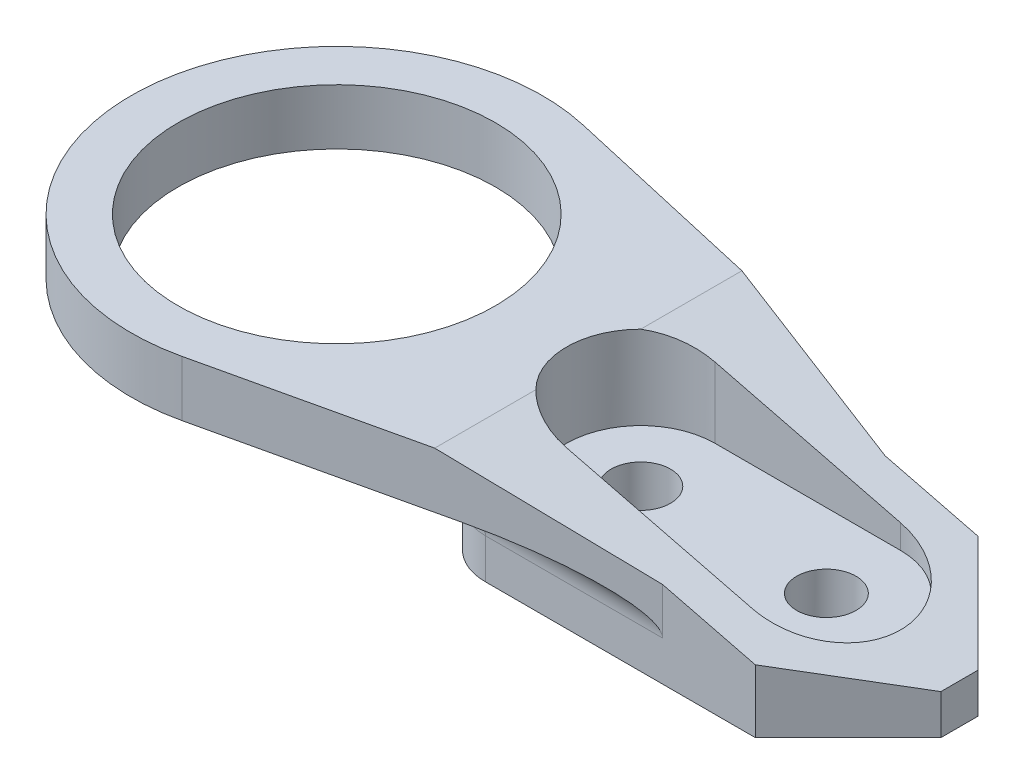
SolidWorks part; units mm, degrees
ref_plane "Front Plane" through (0, 0, 0) normal (0, 0, 1) x (1, 0, 0)
ref_plane "Top Plane" through (0, 0, 0) normal (0, 1, 0) x (1, 0, 0)
ref_plane "Right Plane" through (0, 0, 0) normal (1, 0, 0) x (0, 0, -1)
sketch "Sketch1" plane through (0, 0, 0) normal (0, 0, 1) x (1, 0, 0)
  line L0 (0, 0) -> (0, 7.15)
  line L1 (0, 7.15) -> (25, 7.15)
  line L2 (25, 7.15) -> (25, 0)
  line L3 (25, 0) -> (0, 0)
extrude "Boss-Extrude1" add sketch "Sketch1" along normal blind 12
sketch "Sketch2" plane through (0, 7.15, 0) normal (0, 1, 0) x (1, 0, 0)
  line L0 (0, -6) -> (-8.5537, -6) construction
  line L1 (0, -12) -> (0, 0) construction
  line L3 (25, 0) -> (0, 0) construction
  line L5 (25, -12) -> (0, -12) construction
  line L8 (15, -6) -> (15, 0)
  line L11 (15, 0) -> (-6.0937, 4.8033)
  line L12 (15, -6) -> (15, -12)
  line L13 (15, -12) -> (-6.0937, -16.8033)
  arc A6 (-6.0937, 4.8033) -> (-6.0937, -16.8033) centre (-8.5537, -6) ccw
  line M4 (25, 0) -> (0, 0)
  line M5 (0, 0) -> (0, -12)
  line M6 (0, -12) -> (25, -12)
extrude "Boss-Extrude2" add sketch "Sketch2" against normal blind 3 contours M6 M5 M4 region at (-7.3107, 7.15, 6)
sketch "Sketch3" plane through (0, 4.15, 0) normal (0, -1, 0) x (1, 0, 0)
  circle A1 centre (-8.2201, 6) radius 11
extrude "Cut-Extrude1" cut sketch "Sketch3" along normal blind 21
fillet "Fillet1" radius 3 2 edges at (0.9994, 2.075, 0) (0.9994, 2.075, 12)
sketch "Sketch4" plane through (0, 4.15, 0) normal (0, -1, 0) x (1, 0, 0)
  circle A1 centre (-8.5537, 6) radius 8.55
extrude "Cut-Extrude2" cut sketch "Sketch4" against normal blind 10
chamfer "Chamfer1" distance 5 distance2 20 1 edges at (25, 7.15, 6) first distance on face at (25, 3.575, 6)
sketch "Sketch5" plane through (0, 0, 0) normal (0, -1, 0) x (-1, 0, 0)
  line L0 (-2.4547, -9) -> (-2.4547, -3)
  line L1 (-2.4547, -3) -> (-3.7108, -3)
  line L2 (-3.7108, -3) -> (-3.7108, -9)
  line L3 (-3.7108, -9) -> (-2.4547, -9)
  arc A0 (-5.4547, -12) -> (-2.5244, -8.3571) centre (-5.4547, -9) ccw construction
  arc A1 (-2.5244, -3.6429) -> (-5.4547, 0) centre (-5.4547, -3) ccw construction
extrude "Boss-Extrude3" add sketch "Sketch5" against normal blind 5
fillet "Fillet2" radius 2 5 edges at (10.2273, 4.15, 0) (10.2273, 4.15, 12) (3.3334, 4.15, 11.1213) (2.4547, 4.15, 6) (3.3334, 4.15, 0.8787)
chamfer "Chamfer2" distance 5 angle 45 2 edges at (25, 1.075, 12) (25, 1.075, 0)
sketch "Sketch6" plane through (0, 7.15, 0) normal (0, 1, 0) x (1, 0, 0)
  line L0 (-0.0037, -6) -> (7.8299, -6) construction
  line L1 (7.8299, -6) -> (17.8299, -6) construction
  circle A0 centre (-8.5537, -6) radius 8.55 construction
  circle A1 centre (7.8299, -6) radius 1.6
  circle A2 centre (17.8299, -6) radius 1.6
  dimension "D1" = 10
extrude "Cut-Extrude3" cut sketch "Sketch6" against normal blind 10
sketch "Sketch7" plane through (0, 7.15, 0) normal (0, 1, 0) x (1, 0, 0)
  line L0 (7.8299, -2) -> (17.8299, -2)
  line L1 (17.8299, -10) -> (7.8299, -10)
  arc A0 (7.8299, -2) -> (7.8299, -10) centre (7.8299, -6) ccw
  arc A1 (17.8299, -10) -> (17.8299, -2) centre (17.8299, -6) ccw
extrude "Cut-Extrude4" cut sketch "Sketch7" against normal blind 4.5
